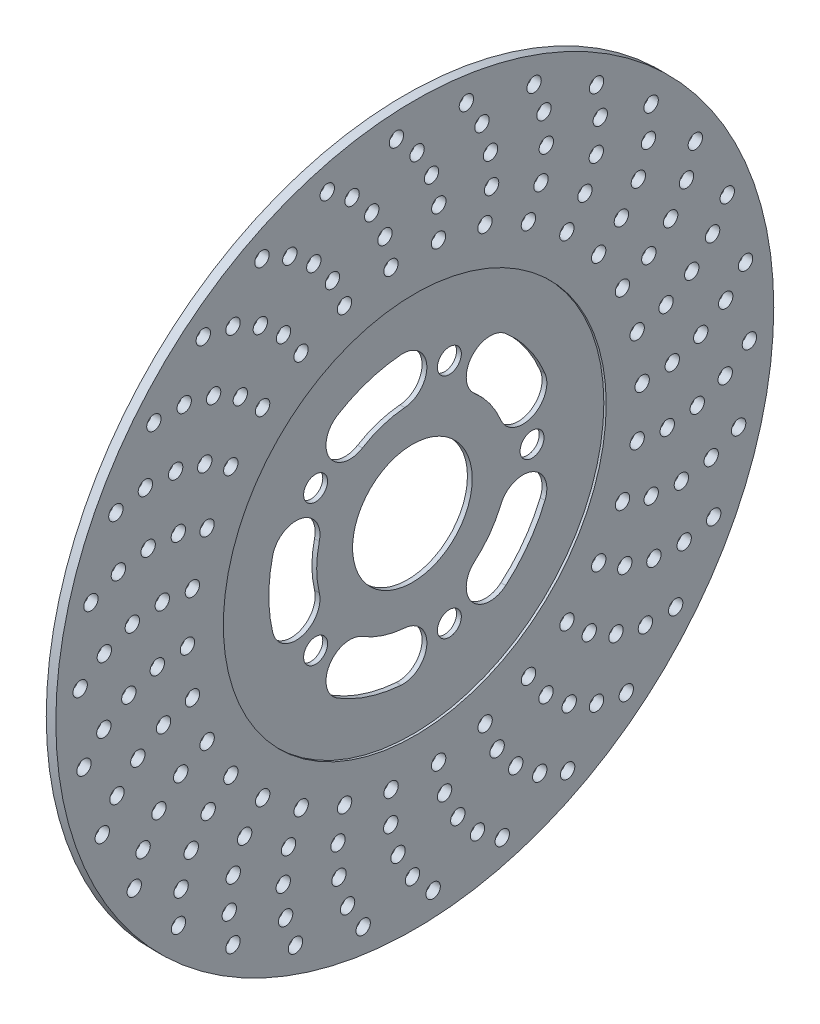
SolidWorks part; units mm, degrees
material "AISI 304"
ref_plane "Front Plane" through (0, 0, 0) normal (1, 0, 0) x (0, 1, 0)
ref_plane "Top Plane" through (0, 0, 0) normal (0, 0, 1) x (0, 1, 0)
ref_plane "Right Plane" through (0, 0, 0) normal (0, 1, 0) x (-1, 0, 0)
sketch "Sketch1" plane through (0, 0, 0) normal (1, 0, 0) x (0, 1, 0)
  line L0 (-112.8184, 0) -> (148.4018, 0) construction
  line L1 (0, 127.9014) -> (0, -119.9572) construction
  line L2 (0, 0) -> (-19.2907, 41.3691) construction
  line L3 (0, 0) -> (18.8398, 40.4021) construction
  circle A0 centre (0, 0) radius 150
  circle A1 centre (0, 0) radius 80
  circle A3 centre (0, 0) radius 25
  circle A4 centre (0, -50) radius 5
  arc A5 (-60, 0) -> (60, 0) centre (0, 0) ccw
  arc A6 (9.3127, 38.9008) -> (-9.3127, 38.9008) centre (0, 0) ccw
  arc A7 (9.3127, 38.9008) -> (13.9691, 58.3512) centre (11.6409, 48.626) ccw
  arc A8 (-13.9691, 58.3512) -> (-9.3127, 38.9008) centre (-11.6409, 48.626) ccw
  arc A9 (-25.3571, 54.3785) -> (-60, 0) centre (0, 0) ccw construction
  arc A10 (13.9691, 58.3512) -> (-13.9691, 58.3512) centre (0, 0) ccw
  arc A11 (60, 0) -> (25.3571, 54.3785) centre (0, 0) ccw construction
  arc A12 (40, 0) -> (16.9047, 36.2523) centre (0, 0) ccw construction
  arc A13 (-40, 0) -> (40, 0) centre (0, 0) ccw
  arc A14 (-16.9047, 36.2523) -> (-40, 0) centre (0, 0) ccw construction
  arc A15 (-13.9691, 58.3512) -> (-25.3571, 54.3785) centre (0, 0) ccw construction
  arc A16 (25.3571, 54.3785) -> (13.9691, 58.3512) centre (0, 0) ccw construction
  arc A17 (16.9047, 36.2523) -> (9.3127, 38.9008) centre (0, 0) ccw construction
  arc A18 (-9.3127, 38.9008) -> (-16.9047, 36.2523) centre (0, 0) ccw construction
  dimension "D1" = 300
  dimension "D2" = 160
  dimension "D3" = 50
  dimension "D5" = 10
  dimension "D6" = 120
  dimension "D7" = 80
  dimension "D8" = 25
  dimension "D4" = 50
  dimension "D9" = 25
extrude "Boss-Extrude1" add sketch "Sketch1" along normal mid plane 4 contours A0 | A1
extrude "Boss-Extrude2" add sketch "Sketch1<3>" along normal mid plane 2 contours A1 A10 A7 A6 A8 A4 A3 | A4 | A6 A8 A10 A7 region at (0, -77.7373, 0)
sketch "Sketch1<3>" plane through (0, 0, 0) normal (1, 0, 0) x (0, 1, 0) same geometry as "Sketch1"
extrude "Cut-Extrude1" cut sketch "Sketch1<4>" against normal through all both and the other way through all contours A7 A10 A8 A6 | A4 region at (0, 0, -50) region at (0, 0, 49.1745)
sketch "Sketch1<4>" plane through (0, 0, 0) normal (1, 0, 0) x (0, 1, 0) same geometry as "Sketch1"
pattern_circular "CirPattern1" count 5 over 360 about axis through (1, 0, 0) along (1, 0, 0) of "Cut-Extrude1"
sketch "Sketch2" plane through (2, 0, 0) normal (1, 0, 0) x (0, 1, 0)
  line L0 (0, 103.6913) -> (0, -78.0626) construction
  line L1 (-110.3359, 0) -> (113.646, 0) construction
  circle A1 centre (0, 0) radius 140 construction
  circle A2 centre (0, 0) radius 95 construction
  arc A3 (0, 96.6353) -> (-22.2413, 138.222) centre (-50, 96.6353) ccw
  circle A4 centre (-22.2413, 138.222) radius 3
  arc A5 (-1.6009, 84.0843) -> (-12.691, 129.9225) centre (-50, 96.6353) ccw
  circle A6 centre (-12.691, 129.9225) radius 3
  arc A7 (-6.3011, 72.337) -> (-5.5298, 119.4914) centre (-50, 96.6353) ccw
  circle A8 centre (-5.5298, 119.4914) radius 3
  arc A9 (-13.7996, 62.1457) -> (-1.2163, 107.5966) centre (-50, 96.6353) ccw
  circle A10 centre (-1.2163, 107.5966) radius 3
  arc A11 (-23.6163, 54.163) -> (-0.0267, 95) centre (-50, 96.6353) ccw
  circle A12 centre (-0.0267, 95) radius 3
  dimension "D2" = 280
  dimension "D4" = 190
  dimension "D5" = 50
  dimension "D6" = 6
  dimension "D7" = 5
  dimension "D8" = 11.0286
extrude "Cut-Extrude2" cut sketch "Sketch2" against normal through all both and the other way through all contours A4 | A5 A6 A3 | A3 A6 A5 | A7 A8 A5 | A5 A8 A7 | A9 A10 A7 | A7 A10 A9 | A11 A12 A9 A3 | A12 A11 A3 A9 region at (2, -1.3154, 95.0422) region at (2, 1.2295, 94.9589) region at (2, -25.0181, 139.1093) region at (2, -13.653, 129.0641) region at (2, -11.7531, 130.7593) region at (2, -6.6765, 118.902) region at (2, -4.4119, 120.0659) region at (2, -2.4743, 107.314) region at (2, 0.01, 107.8722)
pattern_circular "CirPattern2" count 30 over 360 about axis through (2, 0, 0) along (1, 0, 0) of "Cut-Extrude2"
